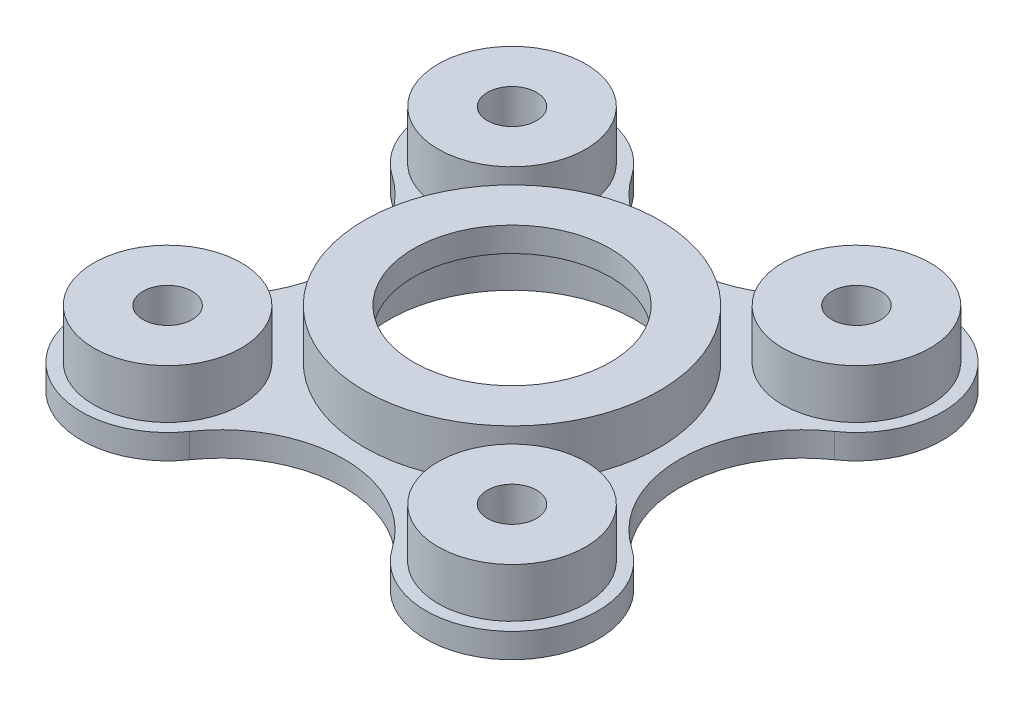
SolidWorks part; units mm, degrees
ref_plane "Front Plane" through (0, 0, 0) normal (0, 0, 1) x (1, 0, 0)
ref_plane "Top Plane" through (0, 0, 0) normal (0, 1, 0) x (1, 0, 0)
ref_plane "Right Plane" through (0, 0, 0) normal (1, 0, 0) x (0, 0, -1)
sketch "Sketch1" plane through (0, 0, 0) normal (0, 1, 0) x (1, 0, 0)
  line L0 (0, 0) -> (-19.3467, 19.3467) construction
  line L5 (0, 0) -> (-5, 0) construction
  circle A0 centre (0, 0) radius 5
  arc A1 (-4.1176, 8.9855) -> (-8.9855, 4.1176) centre (-7, 7) ccw
  circle A2 centre (-7, 7) radius 1
  circle A3 centre (7, 7) radius 1
  circle A4 centre (7, -7) radius 1
  circle A5 centre (-7, -7) radius 1
  arc A6 (8.9855, 4.1176) -> (4.1176, 8.9855) centre (7, 7) ccw
  arc A7 (4.1176, -8.9855) -> (8.9855, -4.1176) centre (7, -7) ccw
  arc A8 (-8.9855, -4.1176) -> (-4.1176, -8.9855) centre (-7, -7) ccw
  arc A9 (4.1176, -8.9855) -> (-4.1176, -8.9855) centre (0, -11.8218) ccw
  arc A10 (-8.9855, -4.1176) -> (-8.9855, 4.1176) centre (-11.8218, 0) ccw
  arc A11 (-4.1176, 8.9855) -> (4.1176, 8.9855) centre (0, 11.8218) ccw
  arc A12 (8.9855, 4.1176) -> (8.9855, -4.1176) centre (11.8218, 0) ccw
  point P20 (0, 0)
  point P23 (0, 0)
  point P33 (0, 0)
  point P55 (0, 0)
  point P84 (0, 0)
  dimension "D5" = 7
  dimension "D8" = 45
  dimension "D6" = 4
extrude "Boss-Extrude1" add sketch "Sketch1" along normal blind 1 contours A2 A5 A4 A3 | A0 region at (0, 0, -6.5248)
sketch "Sketch3" plane through (0, 1, 0) normal (0, 1, 0) x (1, 0, 0)
  circle A0 centre (0, 0) radius 6
extrude "Boss-Extrude2" add sketch "Sketch3" along normal blind 2
sketch "Sketch4" plane through (0, 1, 0) normal (0, -1, 0) x (1, 0, 0)
  circle A0 centre (0, 0) radius 5
extrude "Cut-Extrude1" cut sketch "Sketch4" against normal blind 1
sketch "Sketch5" plane through (0, 2, 0) normal (0, -1, 0) x (1, 0, 0)
  circle A0 centre (0, 0) radius 4
extrude "Cut-Extrude2" cut sketch "Sketch5" against normal blind 1
sketch "Sketch6" plane through (0, 1, 0) normal (0, 1, 0) x (1, 0, 0)
  circle A0 centre (-7, 7) radius 3
  circle A1 centre (7, 7) radius 3
  circle A2 centre (7, -7) radius 3
  circle A3 centre (-7, -7) radius 3
  point P12 (0, 0)
  dimension "D1" = 4
extrude "Boss-Extrude3" add sketch "Sketch6" along normal blind 2
sketch "Sketch7" plane through (0, 1, 0) normal (0, -1, 0) x (1, 0, 0)
  circle A0 centre (-7, 7) radius 1
  circle A1 centre (7, 7) radius 1
  circle A2 centre (7, -7) radius 1
  circle A3 centre (-7, -7) radius 1
  point P12 (0, 0)
  dimension "D1" = 4
extrude "Cut-Extrude3" cut sketch "Sketch7" against normal blind 2
ref_axis "Axis1" through (-7, 1, 7) along (0, -1, 0)
ref_axis "Axis2" through (0, 3, 0) along (0, -1, 0)
ref_axis "Axis3" through (7, 1, 7) along (0, -1, 0)
ref_axis "Axis4" through (7, 1, -7) along (0, -1, 0)
ref_axis "Axis5" through (-7, 1, -7) along (0, -1, 0)
ref_axis "Axis6" through (-4.1176, 1, 8.9855) along (1, 0, 0)
